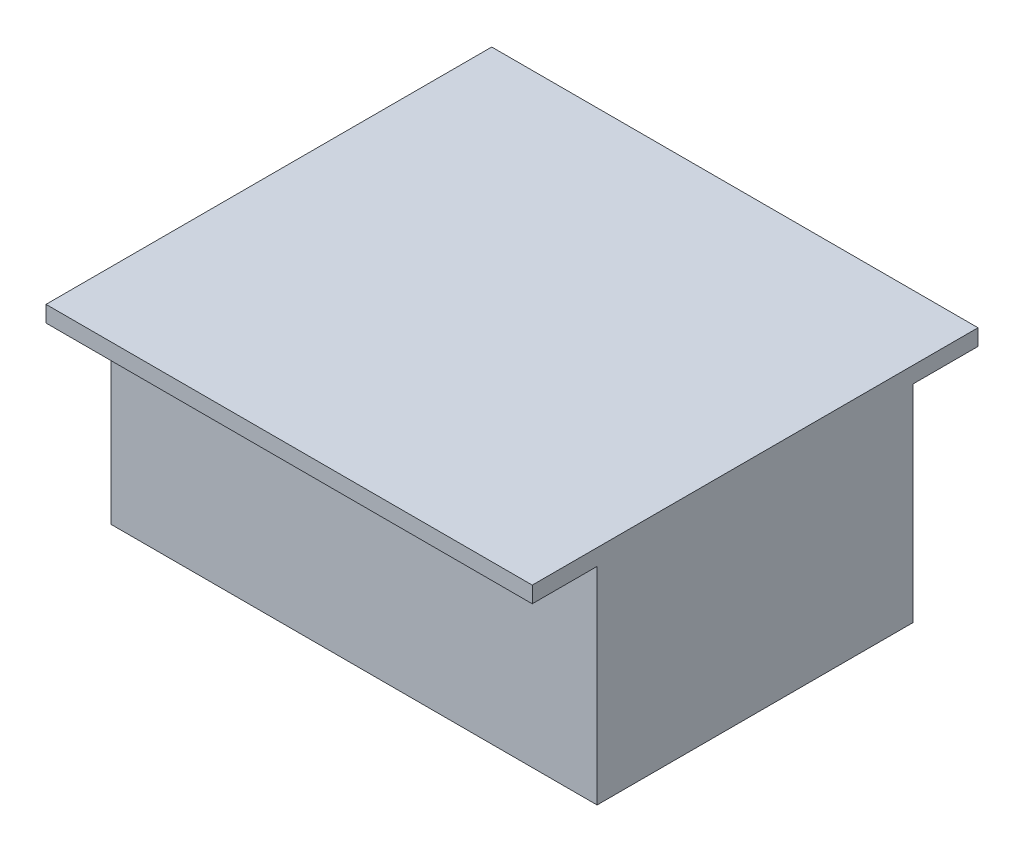
SolidWorks part; units mm, degrees
ref_plane "Přední" through (0, 0, 0) normal (0, 0, 1) x (1, 0, 0)
ref_plane "Horní" through (0, 0, 0) normal (0, 1, 0) x (1, 0, 0)
ref_plane "Pravá" through (0, 0, 0) normal (1, 0, 0) x (0, 0, -1)
sketch "Skica1" plane through (0, 1.6, 0) normal (0, 1, 0) x (1, 0, 0)
  line L0 (1.524, 65.776) -> (1.524, 8.636) construction
  line L1 (-4.318, 76.206) -> (115.682, 76.206)
  line L2 (-4.318, 76.206) -> (-4.318, -1.794)
  line L3 (-4.318, -1.794) -> (115.682, -1.794)
  line L4 (115.682, 76.206) -> (115.682, -1.794)
  line L6 (-4.318, 37.206) -> (1.524, 37.206) construction
  line L7 (1.524, 65.776) -> (1.524, 8.636) construction
  dimension "D1" = 78
  dimension "D2" = 120
  dimension "D3" = 5.842
extrude "Přidat vysunutím1" add sketch "Skica1" against normal blind 55 from offset 14
sketch "Skica2" plane through (0, 15.6, 0) normal (0, 1, 0) x (1, 0, 0)
  line L0 (-4.318, 76.206) -> (-4.318, -1.794) construction
  line L1 (-4.318, 92.206) -> (115.682, 92.206)
  line L2 (-4.318, 92.206) -> (-4.318, -17.794)
  line L3 (-4.318, -17.794) -> (115.682, -17.794)
  line L4 (115.682, 92.206) -> (115.682, -17.794)
  line L5 (115.682, -1.794) -> (115.682, 76.206) construction
  line L6 (115.682, 37.206) -> (-4.318, 37.206) construction
  dimension "D1" = 110
extrude "Přidat vysunutím2" add sketch "Skica2" against normal blind 4
shell "Skořepina1" thickness 2 removed face at (55.682, -39.4, -37.206)
